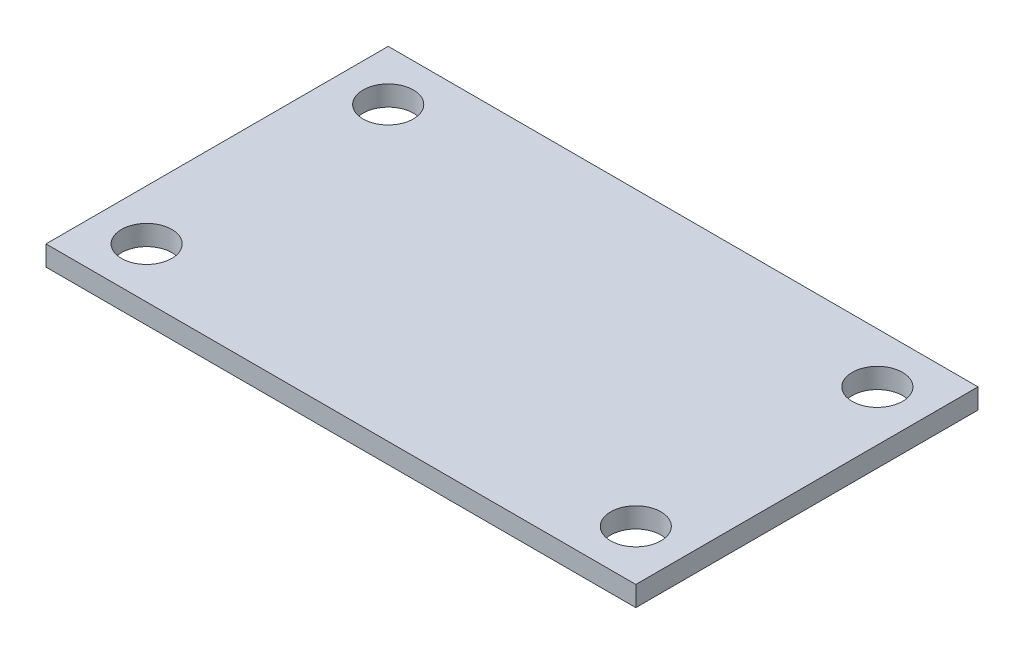
SolidWorks part; units mm, degrees
ref_plane "前视基准面" through (0, 0, 0) normal (0, 0, 1) x (1, 0, 0)
ref_plane "上视基准面" through (0, 0, 0) normal (0, 1, 0) x (1, 0, 0)
ref_plane "右视基准面" through (0, 0, 0) normal (1, 0, 0) x (0, 0, -1)
sketch "草图1" plane through (0, 0, 0) normal (0, 1, 0) x (1, 0, 0)
  line L1 (-14.65, 8.5) -> (14.65, 8.5)
  line L2 (-14.65, 8.5) -> (-14.65, -8.5)
  line L3 (-14.65, -8.5) -> (14.65, -8.5)
  line L4 (14.65, 8.5) -> (14.65, -8.5)
  line L5 (0, -8.5) -> (0, 8.5) construction
  line L6 (-14.65, 0) -> (14.65, 0) construction
  point P0 (0, 0)
  dimension "D1" = 29.3
  dimension "D2" = 17
extrude "凸台-拉伸1" add sketch "草图1" along normal blind 1
sketch "草图2" plane through (0, 1, 0) normal (0, 1, 0) x (1, 0, 0)
  line L0 (0, 11.303) -> (0, -11.7761) construction
  line L1 (-19.5042, 0) -> (17.8745, 0) construction
  circle A0 centre (-12.15, 6) radius 1.25
  circle A1 centre (12.15, 6) radius 1.25
  circle A2 centre (12.15, -6) radius 1.25
  circle A3 centre (-12.15, -6) radius 1.25
  dimension "D1" = 2.5
  dimension "D2" = 24.3
  dimension "D3" = 12
extrude "切除-拉伸1" cut sketch "草图2" against normal blind 1
equation "\"m\"= 2"
